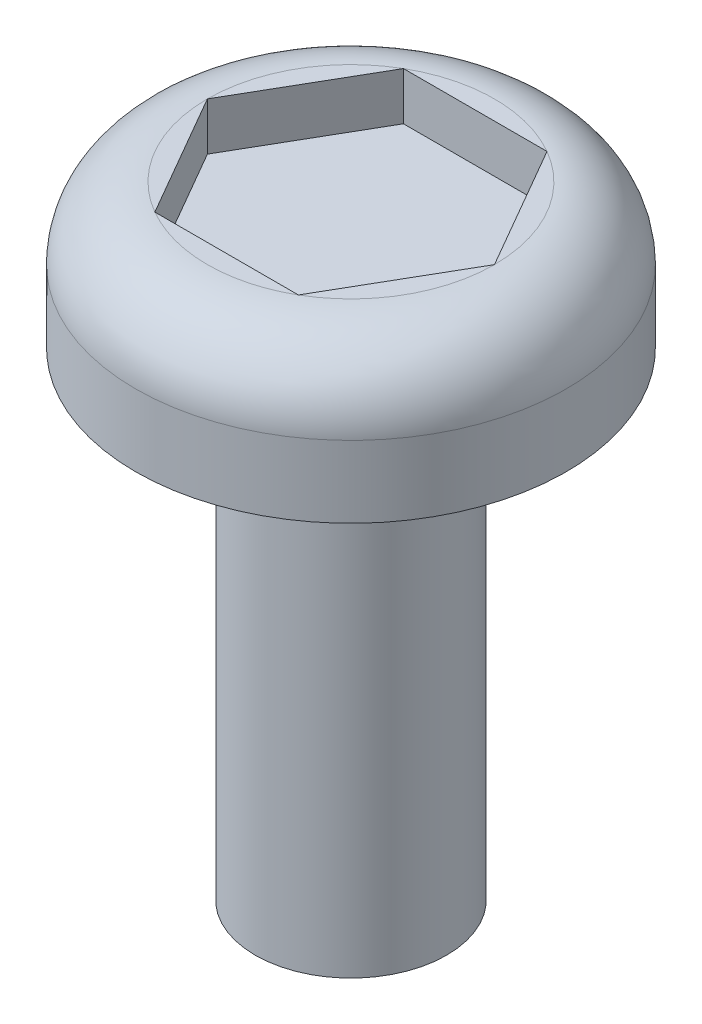
SolidWorks part; units mm, degrees
ref_plane "Front" through (0, 0, 0) normal (0, 0, 1) x (1, 0, 0)
ref_plane "Top" through (0, 0, 0) normal (0, 1, 0) x (1, 0, 0)
ref_plane "Right" through (0, 0, 0) normal (1, 0, 0) x (0, 0, -1)
sketch "Sketch1" plane through (0, 0, 0) normal (0, 1, 0) x (1, 0, 0)
  circle A0 centre (0, 0) radius 1
  dimension "D1" = 2
extrude "Boss-Extrude1" add sketch "Sketch1" along normal blind 5
sketch "Sketch2" plane through (0, 5, 0) normal (0, 1, 0) x (1, 0, 0)
  circle A0 centre (0, 0) radius 2.25
  dimension "D1" = 4.5
extrude "Boss-Extrude2" add sketch "Sketch2" along normal blind 1.5
fillet "Fillet1" radius 0.75 1 edges at (0, 6.5, 2.25)
sketch "Sketch3" plane through (0, 6.5, 0) normal (0, 1, 0) x (1, 0, 0)
  line L1 (1.5, 0) -> (0.75, 1.299)
  line L2 (0.75, 1.299) -> (-0.75, 1.299)
  line L3 (-0.75, 1.299) -> (-1.5, 0)
  line L4 (-1.5, 0) -> (-0.75, -1.299)
  line L5 (-0.75, -1.299) -> (0.75, -1.299)
  line L6 (0.75, -1.299) -> (1.5, 0)
  circle A0 centre (0, 0) radius 1.299 construction
  circle A1 centre (0, 0) radius 1.5 construction
extrude "Cut-Extrude1" cut sketch "Sketch3" against normal blind 0.5
